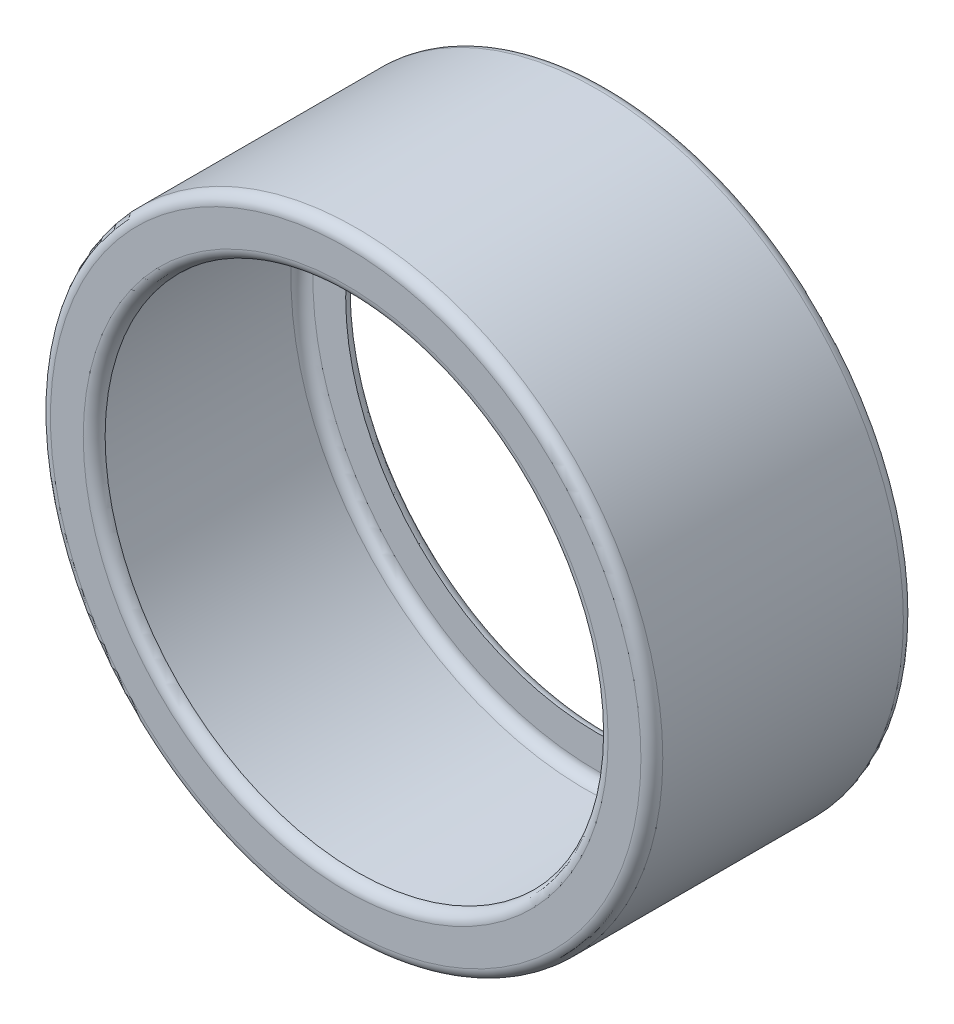
SolidWorks part; units mm, degrees
ref_plane "Front Plane" through (0, 0, 0) normal (0, 0, 1) x (1, 0, 0)
ref_plane "Top Plane" through (0, 0, 0) normal (0, 1, 0) x (1, 0, 0)
ref_plane "Right Plane" through (0, 0, 0) normal (1, 0, 0) x (0, 0, -1)
sketch "Sketch1" plane through (0, 0, 0) normal (0, 0, 1) x (1, 0, 0)
  circle A0 centre (0, 0) radius 28
  circle A1 centre (0, 0) radius 23
  dimension "D1" = 5
  dimension "D2" = 46
extrude "Boss-Extrude1" add sketch "Sketch1" along normal blind 24
fillet "Fillet1" radius 1 4 edges at (23, 0, 0) (23, 0, 24) (28, 0, 0) (28, 0, 24)
shell "Shell1" thickness 1 removed face at (23, 0, 1)
fillet "Fillet2" radius 1 2 edges at (27, 0, 23) (27, 0, 1)
